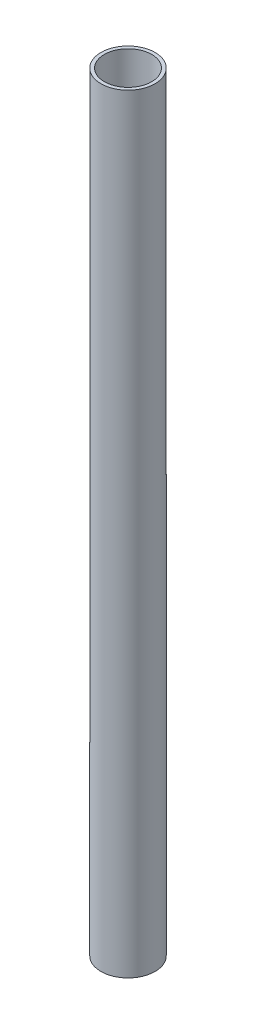
SolidWorks part; units mm, degrees
ref_plane "Front Plane" through (0, 0, 0) normal (0, 0, 1) x (1, 0, 0)
ref_plane "Top Plane" through (0, 0, 0) normal (0, 1, 0) x (1, 0, 0)
ref_plane "Right Plane" through (0, 0, 0) normal (1, 0, 0) x (0, 0, -1)
sketch "Sketch1" plane through (0, 0, 0) normal (0, 1, 0) x (1, 0, 0)
  circle A0 centre (0, 0) radius 8
  circle A1 centre (0, 0) radius 7
extrude "Boss-Extrude1" add sketch "Sketch1" along normal blind 243.065
sketch "Sketch3" plane through (0, 243.065, 0) normal (0, 1, 0) x (1, 0, 0)
  circle A1 centre (0, 0) radius 8
  circle A2 centre (0, 0) radius 8
  dimension "D1" = 0
extrude "Cut-Extrude1" cut sketch "Sketch3" against normal blind 18.23
sketch "Sketch4" plane through (0, 0, 0) normal (0, -1, 0) x (1, 0, 0)
  circle A1 centre (0, 0) radius 8
  circle A2 centre (0, 0) radius 0.4208
  circle A3 centre (0, 0) radius 7
  circle M2 centre (0, 0) radius 8
  circle M3 centre (0, 0) radius 7
extrude "Boss-Extrude2" add sketch "Sketch4" along normal blind 2.36 contours M2 M3 region at (-7.7737, 0, 0)
